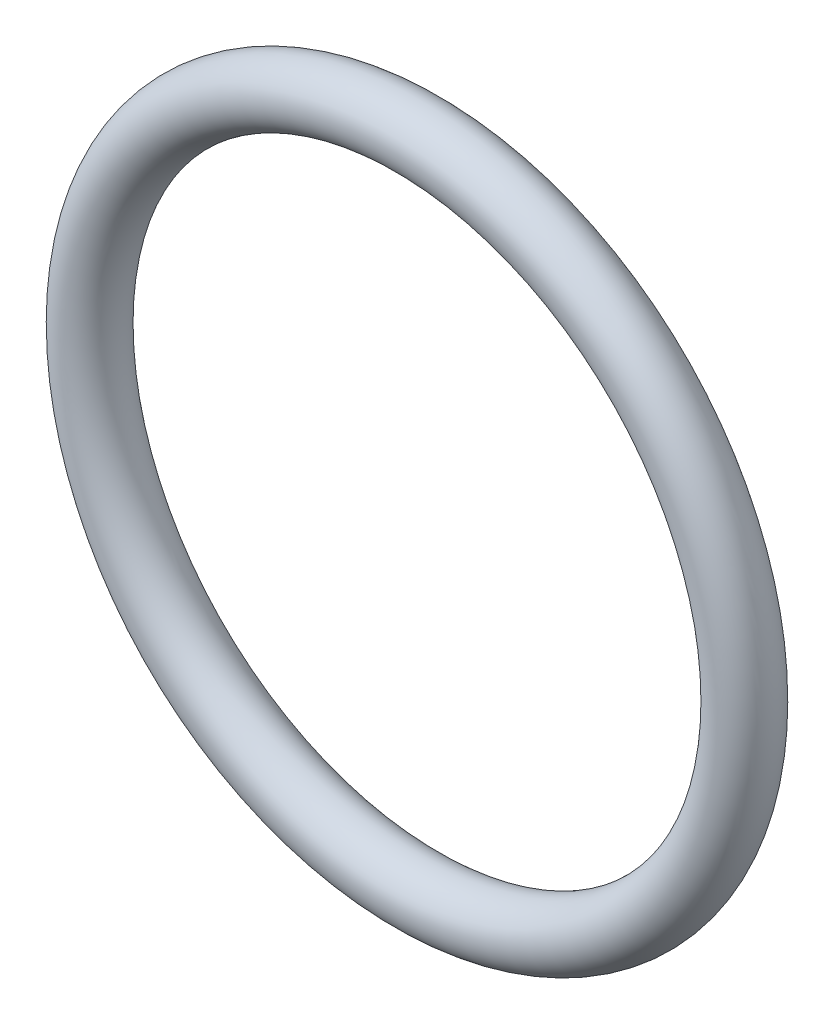
SolidWorks part; units mm, degrees
ref_plane "Front" through (0, 0, 0) normal (0, 0, 1) x (1, 0, 0)
ref_plane "Top" through (0, 0, 0) normal (0, 1, 0) x (1, 0, 0)
ref_plane "Right" through (0, 0, 0) normal (1, 0, 0) x (0, 0, -1)
sketch "Sketch1" plane through (0, 0, 0) normal (1, 0, 0) x (0, -1, 0)
  line L0 (0, -0.889) -> (0, 0.889) construction
  line L2 (-11.3995, 0) -> (11.3995, 0) construction
  line L3 (-8.5852, 0) -> (8.5852, 0) construction
  circle A0 centre (9.4742, 0) radius 0.889
  point P9 (8.5852, 0)
  point P10 (10.3632, 0)
  point P13 (9.4742, 0.889)
  point P14 (9.4742, -0.889)
  dimension "Width" = 1.778
  dimension "ID" = 17.1704
revolve "Revolve1" add sketch "Sketch1" angle 360 about L0
ref_axis "Axis1" through (0, 0, -0.9779) along (0, 0, 1)
